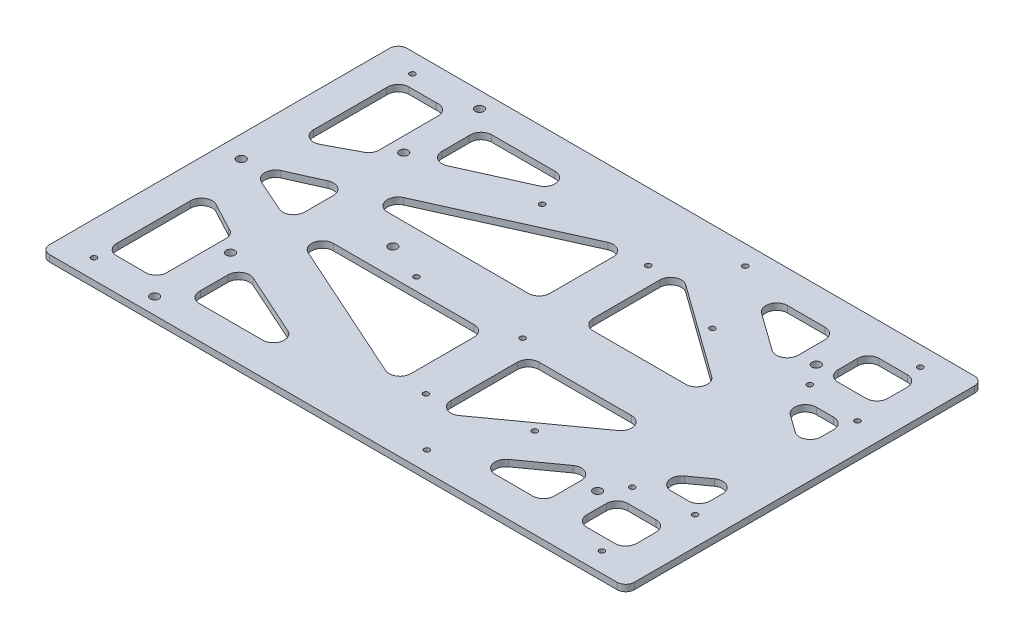
SolidWorks part; units mm, degrees
material "Aleación 1060"
ref_plane "Alzado" through (0, 0, 0) normal (0, 0, 1) x (1, 0, 0)
ref_plane "Planta" through (0, 0, 0) normal (0, 1, 0) x (1, 0, 0)
ref_plane "Vista lateral" through (0, 0, 0) normal (1, 0, 0) x (0, 0, -1)
sketch "Croquis1" plane through (0, 0, 0) normal (0, 1, 0) x (1, 0, 0)
  line L1 (135, -82.5) -> (-135, -82.5)
  line L2 (135, -82.5) -> (135, 82.5)
  line L3 (135, 82.5) -> (-135, 82.5)
  line L4 (-135, -82.5) -> (-135, 82.5)
  line L5 (135, -82.5) -> (-135, 82.5) construction
  line L6 (135, 82.5) -> (-135, -82.5) construction
  point P0 (0, 0)
  dimension "D1" = 165
  dimension "D2" = 270
extrude "Saliente-Extruir1" add sketch "Croquis1" along normal blind 3
fillet "Redondeo1" radius 4 4 edges at (-135, 1.5, -82.5) (135, 1.5, -82.5) (135, 1.5, 82.5) (-135, 1.5, 82.5)
sketch "Croquis2" plane through (0, 3, 0) normal (0, 1, 0) x (1, 0, 0)
  line L0 (131, 82.5) -> (-131, 82.5) construction
  line L1 (135, -78.5) -> (135, 78.5) construction
  circle A0 centre (90, 50.5) radius 2
  dimension "D1" = 4
  dimension "D2" = 32
  dimension "D3" = 45
extrude "Cortar-Extruir1" cut sketch "Croquis2" against normal through all
mirror "Simetría1" about plane through (0, 0, 0) normal (0, 0, 1) of "Cortar-Extruir1"
sketch "Croquis3" plane through (0, 3, 0) normal (0, 1, 0) x (1, 0, 0)
  line L0 (-135, 78.5) -> (-135, -78.5) construction
  line L1 (131, 82.5) -> (-131, 82.5) construction
  line L2 (-135, 0) -> (-113.8944, 0) construction
  circle A0 centre (-90, 75) radius 2
  circle A1 centre (-90, -75) radius 2
  dimension "D1" = 4
  dimension "D2" = 45
  dimension "D3" = 7.5
extrude "Cortar-Extruir2" cut sketch "Croquis3" against normal through all
sketch "Croquis4" plane through (0, 3, 0) normal (0, 1, 0) x (1, 0, 0)
  line L0 (0, 82.5) -> (0, -82.5) construction
  line L1 (131, 82.5) -> (-131, 82.5) construction
  line L2 (-131, -82.5) -> (131, -82.5) construction
  line L3 (-135, 0) -> (135, 0) construction
  line L4 (-135, 78.5) -> (-135, -78.5) construction
  line L5 (135, -78.5) -> (135, 78.5) construction
  line L6 (0, -82.5) -> (131, -82.5) construction
  line L7 (135, -82.5) -> (135, 78.5) construction
  line L8 (131, 82.5) -> (0, 82.5) construction
  line L9 (115, 67.5) -> (102.5, 67.5)
  line L12 (110.2817, 0) -> (2.6409, -64.5845) construction
  line L13 (131, 67.5) -> (-131, 67.5) construction
  line L14 (4.9275, 63.2125) -> (110.2817, 0) construction
  line L15 (15, 10) -> (75.5635, 10)
  line L16 (131, 82.5) -> (-131, 82.5) construction
  line L17 (15, -10) -> (75.5635, -10)
  line L18 (10, 51.3381) -> (10, 15)
  line L19 (17.5725, 55.6256) -> (78.136, 19.2875)
  line L20 (78.136, -19.2875) -> (17.5725, -55.6256)
  line L24 (52.1339, 58.2125) -> (74.9275, 44.5363)
  line L29 (15.2174, 80.3624) -> (149.1548, 0) construction
  line L30 (90, 50.5) -> (90, 67.5) construction
  line L31 (149.1548, 0) -> (12.9308, -81.7344) construction
  line L32 (99.9275, 29.5363) -> (112.4275, 22.0363)
  line L34 (82.5, 62.5) -> (82.5, 48.8238)
  line L36 (97.5, 62.5) -> (97.5, 33.8238)
  line L37 (120, 26.3238) -> (120, 62.5)
  line L38 (77.5, 67.5) -> (54.7063, 67.5)
  line L39 (10, -15) -> (10, -51.3381)
  arc A3 (120, 62.5) -> (115, 67.5) centre (115, 62.5) ccw
  arc A4 (120, 26.3238) -> (112.4275, 22.0363) centre (115, 26.3238) cw
  arc A5 (99.9275, 29.5363) -> (97.5, 33.8238) centre (102.5, 33.8238) cw
  arc A6 (102.5, 67.5) -> (97.5, 62.5) centre (102.5, 62.5) ccw
  arc A7 (10, -51.3381) -> (17.5725, -55.6256) centre (15, -51.3381) ccw
  arc A9 (10, 51.3381) -> (17.5725, 55.6256) centre (15, 51.3381) cw
  arc A10 (75.5635, 10) -> (78.136, 19.2875) centre (75.5635, 15) ccw
  arc A11 (75.5635, -10) -> (78.136, -19.2875) centre (75.5635, -15) cw
  arc A12 (15, 10) -> (10, 15) centre (15, 15) cw
  arc A13 (15, -10) -> (10, -15) centre (15, -15) ccw
  arc A14 (82.5, 48.8238) -> (74.9275, 44.5363) centre (77.5, 48.8238) cw
  arc A15 (77.5, 67.5) -> (82.5, 62.5) centre (77.5, 62.5) cw
  arc A16 (52.1339, 58.2125) -> (54.7063, 67.5) centre (54.7063, 62.5) cw
  point P44 (97.5, 30.9929)
  point P64 (10, -10)
  dimension "D5" = 33.6762
  dimension "D6" = 5
  dimension "D7" = 5
  dimension "D13" = 5
  dimension "D14" = 5
  dimension "D15" = 5
  dimension "D16" = 22.0363
  dimension "D2" = 5
  dimension "D4" = 15
  dimension "D8" = 15
  dimension "D10" = 10
  dimension "D11" = 10
  dimension "D12" = 10
  dimension "D3" = 20
  dimension "D1" = 15
extrude "Cortar-Extruir3" [suppressed] cut sketch "Croquis4" against normal through all
mirror "Simetría4" [suppressed] about plane through (0, 0, 0) normal (1, 0, 0)
sketch "Croquis5" plane through (0, 3, 0) normal (0, 1, 0) x (1, 0, 0)
  line L0 (135, -78.5) -> (135, 78.5) construction
  line L1 (-131, -82.5) -> (131, -82.5) construction
  line L2 (131, 82.5) -> (-131, 82.5) construction
  circle A0 centre (-119.5, 73.5) radius 1.75
  circle A1 centre (34.2, 73.5) radius 1.75
  circle A2 centre (115, 73.5) radius 1.75
  circle A3 centre (115, -73.5) radius 1.75
  circle A4 centre (34.2, -73.5) radius 1.75
  circle A5 centre (-119.5, -73.5) radius 1.75
  point P0 (-119.5, 73.5)
  point P3 (34.2, 73.5)
  point P6 (115, 73.5)
  point P9 (115, -73.5)
  point P12 (34.2, -73.5)
  point P15 (-119.5, -73.5)
  dimension "D1" = 20
  dimension "D2" = 80.8
  dimension "D3" = 153.7
  dimension "D4" = 9
  dimension "D5" = 9
hole_wizard "Taladro roscado M31" positions "Croquis5" profile "Croquis6" tap size "M3" standard "ISO"
sketch "Croquis6" plane through (-119.5, 3, -73.5) normal (1, 0, 0) x (0, 0, 1)
  line L0 (0, 0) -> (0, 9.2511)
  line L1 (0, 9.2511) -> (1.25, 8.5)
  line L2 (1.25, 8.5) -> (1.25, 0)
  line L5 (1.25, 0) -> (0, 0)
  line L10 (0, 9.2511) -> (-1.25, 8.5) construction
  line L11 (0, -6.35) -> (0, 107.95) construction
  dimension "Diámetro de perforador para roscar" = 2.5
  dimension "Profundidad de perforador para roscar" = 8.5
  dimension "Ángulo de perforador" = 118
cosmetic thread "Rosca de taladro1" parameters "D1"=6, "D2"=3
cosmetic thread "Rosca de taladro2" parameters "D1"=6, "D2"=3
cosmetic thread "Rosca de taladro3" parameters "D1"=6, "D2"=3
cosmetic thread "Rosca de taladro4" parameters "D1"=6, "D2"=3
cosmetic thread "Rosca de taladro5" parameters "D1"=6, "D2"=3
cosmetic thread "Rosca de taladro6" parameters "D1"=6, "D2"=3
mirror "Simetría5" [suppressed] about plane through (0, 0, 0) normal (0, 0, 1)
mirror "Simetría7" [suppressed] about plane through (0, 0, 0) normal (1, 0, 0)
mirror "Simetría8" [suppressed] about plane through (0, 0, 0) normal (1, 0, 0)
sketch "Croquis9" plane through (0, 3, 0) normal (0, 1, 0) x (1, 0, 0)
  line L0 (-131, -82.5) -> (131, -82.5) construction
  line L2 (-135, 78.5) -> (-135, -78.5) construction
  line L4 (131, 82.5) -> (-131, 82.5) construction
  circle A0 centre (-125, 0) radius 2
  circle A1 centre (-90, 40) radius 2
  circle A2 centre (-55, 0) radius 2
  circle A3 centre (-90, -40) radius 2
  point P1 (-90, -40)
  point P3 (-55, 0)
  dimension "D1" = 4
  dimension "D5" = 10
  dimension "D3" = 82.5
  dimension "D6" = 45
  dimension "D2" = 42.5
  dimension "D4" = 80
  dimension "D7" = 42.5
extrude "Cortar-Extruir4" cut sketch "Croquis9" against normal blind 4
sketch "Croquis10" plane through (0, 3, 0) normal (0, 1, 0) x (1, 0, 0)
  circle A0 centre (0, 0) radius 2
  circle A1 centre (0, 60.1959) radius 2
  circle A2 centre (0, -65.3126) radius 2
  dimension "D1" = 4
extrude "Cortar-Extruir5" [suppressed] cut sketch "Croquis10" against normal through all
sketch "Croquis11" plane through (0, 3, 0) normal (0, 1, 0) x (1, 0, 0)
  point P0 (-37.4183, 51.3035)
  point P1 (11.5817, 51.3035)
  point P3 (11.5817, -6.6965)
  point P5 (-37.4183, -6.6965)
  point P17 (-37.4183, 51.3035)
  point P19 (-37.4183, -6.6965)
  point P21 (11.5817, -6.6965)
  point P23 (11.5817, 51.3035)
  point P32 (0, 0)
  point P33 (0, 0)
hole_wizard "Taladro roscado M33" positions "Croquis11" profile "Croquis13" tap size "M3" standard "ISO"
sketch "Croquis13" plane through (-37.4183, 3, -51.3035) normal (1, 0, 0) x (0, 0, 1)
  line L0 (0, 0) -> (0, 9.2511)
  line L1 (0, 9.2511) -> (1.25, 8.5)
  line L2 (1.25, 8.5) -> (1.25, 0)
  line L5 (1.25, 0) -> (0, 0)
  line L10 (0, 9.2511) -> (-1.25, 8.5) construction
  line L11 (0, -6.35) -> (0, 107.95) construction
  dimension "Diámetro de perforador para roscar" = 2.5
  dimension "Profundidad de perforador para roscar" = 8.5
  dimension "Ángulo de perforador" = 118
cosmetic thread "Rosca de taladro35" parameters "D1"=6, "D2"=3
cosmetic thread "Rosca de taladro36" parameters "D1"=6, "D2"=3
cosmetic thread "Rosca de taladro37" parameters "D1"=6, "D2"=3
cosmetic thread "Rosca de taladro38" parameters "D1"=6, "D2"=3
sketch "Croquis14" plane through (0, 3, 0) normal (0, 1, 0) x (1, 0, 0)
  line L0 (-135, 0) -> (135, 0) construction
  line L1 (-135, 78.5) -> (-135, -78.5) construction
  line L2 (135, -78.5) -> (135, 78.5) construction
  line L3 (0, 82.5) -> (0, -82.5) construction
  line L5 (-131, -82.5) -> (131, -82.5) construction
  line L6 (-120, 28.3988) -> (-120, 62.0179)
  line L7 (-100.1523, 30.6318) -> (-112.6523, 23.9842)
  line L8 (-96.7551, 61.9356) -> (-96.7099, 34.9641)
  line L9 (131, 67.5) -> (-131, 67.5)
  line L10 (120, 67.5) -> (-120, 67.5) construction
  line L11 (-115, 67.5) -> (-102.5, 67.5)
  line L12 (-120, 78.5) -> (-120, -78.5)
  line L13 (-120, 67.5) -> (-120, -67.5) construction
  line L14 (-77.0591, 67.5) -> (-47.6094, 67.5)
  line L15 (-131, -67.5) -> (131, -67.5)
  line L16 (-120, -67.5) -> (120, -67.5) construction
  line L18 (120, -78.5) -> (120, 78.5)
  line L19 (120, -67.5) -> (120, 33.5) construction
  line L25 (115, 67.5) -> (102.0282, 67.5)
  line L31 (-81.7551, 61.9607) -> (-81.734, 49.3949)
  line L32 (-45.5588, 57.9398) -> (-74.6834, 44.8431)
  line L33 (0, 46.7293) -> (0, 17.5)
  line L35 (-5, 12.5) -> (-70, 12.5)
  line L36 (25, 12.5) -> (67.7096, 12.5)
  line L37 (20, 48.2286) -> (20, 17.5)
  line L38 (27.9201, 52.2873) -> (70.6297, 21.5587)
  line L39 (56.7965, 58.4413) -> (74.1081, 45.986)
  line L40 (90, 50.5) -> (90, 67.5) construction
  line L41 (104.053, 24.4413) -> (112.0799, 18.6662)
  line L42 (82.0282, 62.5) -> (82.0282, 50.0447)
  line L43 (97.0282, 62.5) -> (97.0282, 53.5)
  line L44 (120, 22.7248) -> (120, 28.5)
  line L45 (77.0282, 67.5) -> (59.7166, 67.5)
  line L48 (77.0282, -67.5) -> (59.7166, -67.5)
  line L49 (82.0282, -62.5) -> (82.0282, -50.0447)
  line L50 (56.7965, -58.4413) -> (74.1081, -45.986)
  line L51 (20, -48.2286) -> (20, -17.5)
  line L52 (27.9201, -52.2873) -> (70.6297, -21.5587)
  line L53 (25, -12.5) -> (67.7096, -12.5)
  line L54 (-5, -12.5) -> (-70, -12.5)
  line L56 (0, -46.7293) -> (0, -17.5)
  line L57 (-45.5588, -57.9398) -> (-74.6834, -44.8431)
  line L58 (-81.7551, -61.9607) -> (-81.734, -49.3949)
  line L59 (-77.0591, -67.5) -> (-47.6094, -67.5)
  line L60 (-120, -28.3988) -> (-120, -62.0179)
  line L61 (-100.1523, -30.6318) -> (-112.6523, -23.9842)
  line L62 (-96.7551, -61.9356) -> (-96.7099, -34.9641)
  line L63 (-115, -67.5) -> (-102.5, -67.5)
  line L64 (102.0282, 48.5) -> (115, 48.5)
  line L65 (106.9731, 33.5) -> (115, 33.5)
  line L67 (120, 53.5) -> (120, 62.5)
  line L68 (120, 48.5) -> (120, 67.5) construction
  line L69 (120, -53.5) -> (120, -62.5)
  line L70 (102.0282, -48.5) -> (115, -48.5)
  line L71 (97.0282, -62.5) -> (97.0282, -53.5)
  line L72 (115, -67.5) -> (102.0282, -67.5)
  line L73 (106.9731, -33.5) -> (115, -33.5)
  line L74 (120, -22.7248) -> (120, -28.5)
  line L75 (104.053, -24.4413) -> (112.0799, -18.6662)
  line L76 (-7.0506, 51.2894) -> (-72.0506, 22.0602)
  line L77 (-7.0506, -51.2894) -> (-72.0506, -22.0602)
  arc A10 (-120, 62.0179) -> (-115, 67.5) centre (-115.0233, 62.5001) cw
  arc A11 (-120, 28.3988) -> (-112.6523, 23.9842) centre (-115, 28.3988) ccw
  arc A12 (-100.1523, 30.6318) -> (-96.7099, 34.9641) centre (-101.6918, 35.3889) ccw
  arc A13 (-102.5, 67.5) -> (-96.7551, 61.9356) centre (-101.7157, 62.5619) cw
  arc A14 (-45.5588, 57.9398) -> (-47.6094, 67.5) centre (-47.6094, 62.5) ccw
  arc A15 (-77.0591, 67.5) -> (-81.7551, 61.9607) centre (-76.7851, 62.5075) ccw
  arc A16 (-81.734, 49.3949) -> (-74.6834, 44.8431) centre (-76.734, 49.4032) ccw
  arc A17 (-5, 12.5) -> (0, 17.5) centre (-5, 17.5) ccw
  arc A18 (0, 46.7293) -> (-7.0506, 51.2894) centre (-5, 46.7293) ccw
  arc A19 (-70, 12.5) -> (-72.0506, 22.0602) centre (-70, 17.5) cw
  arc A20 (120, 62.5) -> (115, 67.5) centre (115, 62.5) ccw
  arc A21 (120, 22.7248) -> (112.0799, 18.6662) centre (115, 22.7248) cw
  arc A23 (102.0282, 67.5) -> (97.0282, 62.5) centre (102.0282, 62.5) ccw
  arc A24 (20, 48.2286) -> (27.9201, 52.2873) centre (25, 48.2286) cw
  arc A25 (67.7096, 12.5) -> (70.6297, 21.5587) centre (67.7096, 17.5) ccw
  arc A26 (25, 12.5) -> (20, 17.5) centre (25, 17.5) cw
  arc A27 (82.0282, 50.0447) -> (74.1081, 45.986) centre (77.0282, 50.0447) cw
  arc A28 (77.0282, 67.5) -> (82.0282, 62.5) centre (77.0282, 62.5) cw
  arc A29 (56.7965, 58.4413) -> (59.7166, 67.5) centre (59.7166, 62.5) cw
  arc A34 (56.7965, -58.4413) -> (59.7166, -67.5) centre (59.7166, -62.5) ccw
  arc A35 (77.0282, -67.5) -> (82.0282, -62.5) centre (77.0282, -62.5) ccw
  arc A36 (82.0282, -50.0447) -> (74.1081, -45.986) centre (77.0282, -50.0447) ccw
  arc A37 (25, -12.5) -> (20, -17.5) centre (25, -17.5) ccw
  arc A38 (20, -48.2286) -> (27.9201, -52.2873) centre (25, -48.2286) ccw
  arc A39 (67.7096, -12.5) -> (70.6297, -21.5587) centre (67.7096, -17.5) cw
  arc A40 (-70, -12.5) -> (-72.0506, -22.0602) centre (-70, -17.5) ccw
  arc A41 (0, -46.7293) -> (-7.0506, -51.2894) centre (-5, -46.7293) cw
  arc A42 (-5, -12.5) -> (0, -17.5) centre (-5, -17.5) cw
  arc A43 (-81.734, -49.3949) -> (-74.6834, -44.8431) centre (-76.734, -49.4032) cw
  arc A44 (-77.0591, -67.5) -> (-81.7551, -61.9607) centre (-76.7851, -62.5075) cw
  arc A45 (-45.5588, -57.9398) -> (-47.6094, -67.5) centre (-47.6094, -62.5) cw
  arc A46 (-120, -28.3988) -> (-112.6523, -23.9842) centre (-115, -28.3988) cw
  arc A47 (-100.1523, -30.6318) -> (-96.7099, -34.9641) centre (-101.6918, -35.3889) cw
  arc A48 (-102.5, -67.5) -> (-96.7551, -61.9356) centre (-101.7157, -62.5619) ccw
  arc A49 (-120, -62.0179) -> (-115, -67.5) centre (-115.0233, -62.5001) ccw
  arc A51 (115, 48.5) -> (120, 53.5) centre (115, 53.5) ccw
  arc A52 (102.0282, 48.5) -> (97.0282, 53.5) centre (102.0282, 53.5) cw
  arc A53 (115, 33.5) -> (120, 28.5) centre (115, 28.5) cw
  arc A54 (104.053, 24.4413) -> (106.9731, 33.5) centre (106.9731, 28.5) cw
  arc A55 (115, -48.5) -> (120, -53.5) centre (115, -53.5) cw
  arc A56 (102.0282, -48.5) -> (97.0282, -53.5) centre (102.0282, -53.5) ccw
  arc A57 (102.0282, -67.5) -> (97.0282, -62.5) centre (102.0282, -62.5) cw
  arc A58 (120, -62.5) -> (115, -67.5) centre (115, -62.5) cw
  arc A59 (115, -33.5) -> (120, -28.5) centre (115, -28.5) ccw
  arc A60 (120, -22.7248) -> (112.0799, -18.6662) centre (115, -22.7248) ccw
  arc A61 (104.053, -24.4413) -> (106.9731, -33.5) centre (106.9731, -28.5) ccw
  point P161 (91.4624, 33.5)
  dimension "D6" = 5
  dimension "D7" = 5
  dimension "D8" = 5
  dimension "D9" = 5
  dimension "D11" = 5
  dimension "D24" = 5
  dimension "D25" = 5
  dimension "D26" = 5
  dimension "D13" = 5
  dimension "D27" = 5
  dimension "D18" = 5
  dimension "D28" = 5
  dimension "D5" = 15
  dimension "D10" = 21.86
  dimension "D12" = 20
  dimension "D14" = 0
  dimension "D15" = 15
  dimension "D16" = 39.7752
  dimension "D17" = 12.5
  dimension "D19" = 12.5
  dimension "D21" = 65
  dimension "D1" = 15
  dimension "D2" = 15
  dimension "D3" = 15
  dimension "D4" = 15
extrude "Cortar-Extruir6" cut sketch "Croquis14" against normal through all
mirror "Simetría9" about plane through (0, 0, 0) normal (0, 0, 1) of face at (11.5817, 3, -50.0535)
cosmetic thread "Rosca de taladro39" parameters "D1"=6, "D2"=3
sketch "Croquis15" plane through (0, 3, 0) normal (0, 1, 0) x (1, 0, 0)
  line L0 (0, 0) -> (-135, 0) construction
  line L1 (-135, 78.5) -> (-135, -78.5) construction
  line L2 (0, 0) -> (135, 0) construction
  line L3 (-111.1343, -4.5636) -> (-96.167, -11.264)
  line L4 (-81.734, 49.3949) -> (-81.734, -49.3949) construction
  line L5 (-89.124, 6.7004) -> (-89.124, -6.7004)
  line L6 (-89.124, 49.3949) -> (-89.124, -49.3949) construction
  line L7 (-96.167, 11.264) -> (-111.1343, 4.5636)
  line L11 (135, -78.5) -> (135, 78.5) construction
  arc A1 (-96.167, -11.264) -> (-89.124, -6.7004) centre (-94.124, -6.7004) ccw
  arc A2 (-89.124, 6.7004) -> (-96.167, 11.264) centre (-94.124, 6.7004) ccw
  arc A3 (-111.1343, 4.5636) -> (-111.1343, -4.5636) centre (-109.0914, 0) ccw
  point P22 (-121.3284, 0)
  dimension "D2" = 5
  dimension "D1" = 7.39
extrude "Cortar-Extruir7" cut sketch "Croquis15" against normal through all
sketch "Croquis17" plane through (0, 3, 0) normal (0, 1, 0) x (1, 0, 0)
  circle A0 centre (51.5, 41) radius 1.5
  dimension "D1" = 3
sketch "Croquis19" plane through (0, 3, 0) normal (0, 1, 0) x (1, 0, 0)
  circle A0 centre (96.5, 41) radius 1.5
  circle A1 centre (96.5, -41) radius 1.5
  circle A2 centre (51.5, -41) radius 1.5
  point P0 (96.5, 41)
  point P4 (96.5, -41)
  point P7 (51.5, -41)
  point P10 (51.5, 41)
  dimension "D1" = 3
hole_wizard "Taladro roscado M34" positions "Croquis19" profile "Croquis20" tap size "M3" standard "ISO"
sketch "Croquis20" plane through (96.5, 3, -41) normal (1, 0, 0) x (0, 0, 1)
  line L0 (0, 0) -> (0, 9.2511)
  line L1 (0, 9.2511) -> (1.25, 8.5)
  line L2 (1.25, 8.5) -> (1.25, 0)
  line L5 (1.25, 0) -> (0, 0)
  line L10 (0, 9.2511) -> (-1.25, 8.5) construction
  line L11 (0, -6.35) -> (0, 107.95) construction
  dimension "Diámetro de perforador para roscar" = 2.5
  dimension "Profundidad de perforador para roscar" = 8.5
  dimension "Ángulo de perforador" = 118
cosmetic thread "Rosca de taladro40" parameters "D1"=6, "D2"=3
cosmetic thread "Rosca de taladro41" parameters "D1"=6, "D2"=3
cosmetic thread "Rosca de taladro42" parameters "D1"=6, "D2"=3
cosmetic thread "Rosca de taladro43" parameters "D1"=6, "D2"=3
sketch "Croquis21" plane through (0, 3, 0) normal (0, 1, 0) x (1, 0, 0)
  point P0 (122, 37.5)
  point P1 (122, -37.5)
hole_wizard "Taladro roscado M35" positions "Croquis21" profile "Croquis22" tap size "M3" standard "ISO"
sketch "Croquis22" plane through (122, 3, -37.5) normal (1, 0, 0) x (0, 0, 1)
  line L0 (0, 0) -> (0, 9.2511)
  line L1 (0, 9.2511) -> (1.25, 8.5)
  line L2 (1.25, 8.5) -> (1.25, 0)
  line L5 (1.25, 0) -> (0, 0)
  line L10 (0, 9.2511) -> (-1.25, 8.5) construction
  line L11 (0, -6.35) -> (0, 107.95) construction
  dimension "Diámetro de perforador para roscar" = 2.5
  dimension "Profundidad de perforador para roscar" = 8.5
  dimension "Ángulo de perforador" = 118
cosmetic thread "Rosca de taladro44" parameters "D1"=6, "D2"=3
cosmetic thread "Rosca de taladro45" parameters "D1"=6, "D2"=3
